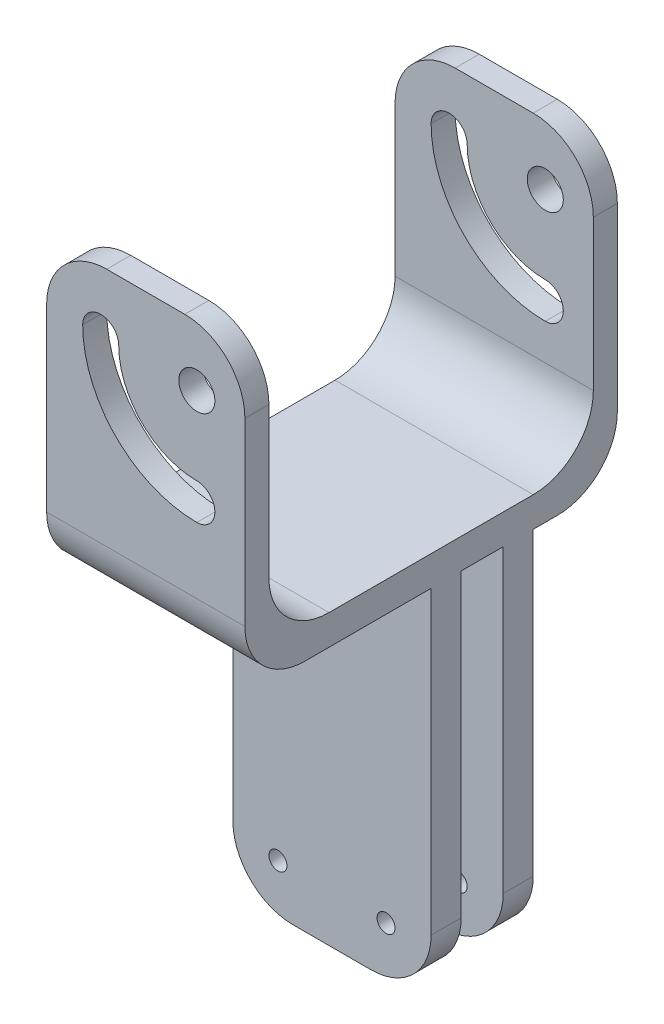
SolidWorks part; units mm, degrees
other "Marcação1"
sketch "Esboço5" plane through (0, 50, 68.25) normal (-0.797, 0.1637, 0.5813) x (0.5636, -0.1442, 0.8134)
material "Nylon - impressão"
ref_plane "Plano frontal" through (0, 0, 0) normal (0, 0, 1) x (1, 0, 0)
ref_plane "Plano superior" through (0, 0, 0) normal (0, 1, 0) x (1, 0, 0)
ref_plane "Plano direito" through (0, 0, 0) normal (1, 0, 0) x (0, 0, -1)
sketch "Esboço1" plane through (0, 0, 0) normal (0, 0, 1) x (1, 0, 0)
  line L0 (0, 0) -> (0, 50)
  line L1 (0, 50) -> (33, 50)
  line L2 (33, 50) -> (33, 0)
  line L3 (33, 0) -> (0, 0)
  line L4 (25, 40) -> (25, 37) construction
  circle A0 centre (25, 40) radius 3
  arc A2 (25, 24) -> (9, 40) centre (25, 40) cw construction
  arc A3 (6, 40) -> (25, 21) centre (25, 40) ccw
  arc A4 (12, 40) -> (25, 27) centre (25, 40) ccw
  arc A5 (12, 40) -> (6, 40) centre (9, 40) ccw
  arc A6 (25, 21) -> (25, 27) centre (25, 24) ccw
  point P10 (13.6863, 28.6863)
  dimension "D3" = 6
  dimension "D5" = 16
  dimension "D6" = 13
  dimension "D1" = 25
  dimension "D2" = 50
  dimension "D4" = 8
extrude "Ressalto-extrusão2" add sketch "Esboço1" along normal blind 62
sketch "Esboço3" plane through (0, 50, 0) normal (0, 1, 0) x (1, 0, 0)
  line L0 (0, -58) -> (33, -58)
  line L1 (0, -62) -> (0, 0) construction
  line L2 (33, -62) -> (33, 0) construction
  line L3 (33, -58) -> (33, -4)
  line L4 (33, -4) -> (0, -4)
  line L5 (0, -4) -> (0, -58)
  line L6 (33, 0) -> (0, 0) construction
  dimension "D1" = 4
  dimension "D2" = 4
extrude "Corte-extrusão1" cut sketch "Esboço3" against normal blind 45
sketch "Esboço7" plane through (0, 0, 0) normal (0, -1, 0) x (1, 0, 0)
  line L0 (0, 14) -> (33, 14)
  line L1 (0, 62) -> (0, 0) construction
  line L2 (33, 62) -> (33, 0) construction
  line L3 (33, 14) -> (33, 19)
  line L4 (33, 19) -> (0, 19)
  line L5 (0, 19) -> (0, 14)
  line L6 (0, 26) -> (33, 26)
  line L7 (33, 26) -> (33, 31)
  line L8 (33, 31) -> (0, 31)
  line L9 (0, 31) -> (0, 26)
  dimension "D1" = 5
  dimension "D2" = 5
  dimension "D3" = 7
extrude "Ressalto-extrusão3" add sketch "Esboço7" along normal blind 60
sketch "Esboço10" plane through (0, 0, 14) normal (0, 0, -1) x (-1, 0, 0)
  line L2 (0, -60) -> (-33, -60) construction
  line L3 (-7.5, -52) -> (-25.5, -52) construction
  line L4 (0, 0) -> (-33, 0) construction
  circle A5 centre (-25.5, -52) radius 1.5
  circle A6 centre (-7.5, -52) radius 1.5
  point P0 (-16.5, -52)
  point P1 (0, 0)
  point P2 (-16.5, 0)
  dimension "D7" = 3
  dimension "D8" = 3
  dimension "D10" = 18
  dimension "D11" = 8
extrude "Corte-extrusão2" cut sketch "Esboço10" against normal through all
fillet "Filete1" radius 10 12 edges at (16.5, 5, 4) (0, 50, 2) (33, 50, 2) (16.5, 5, 58) (16.5, 0, 62) (16.5, 0, 0) (33, -60, 28.5) (33, -60, 16.5) (0, -60, 16.5) (0, -60, 28.5) (0, 50, 60) (33, 50, 60)
